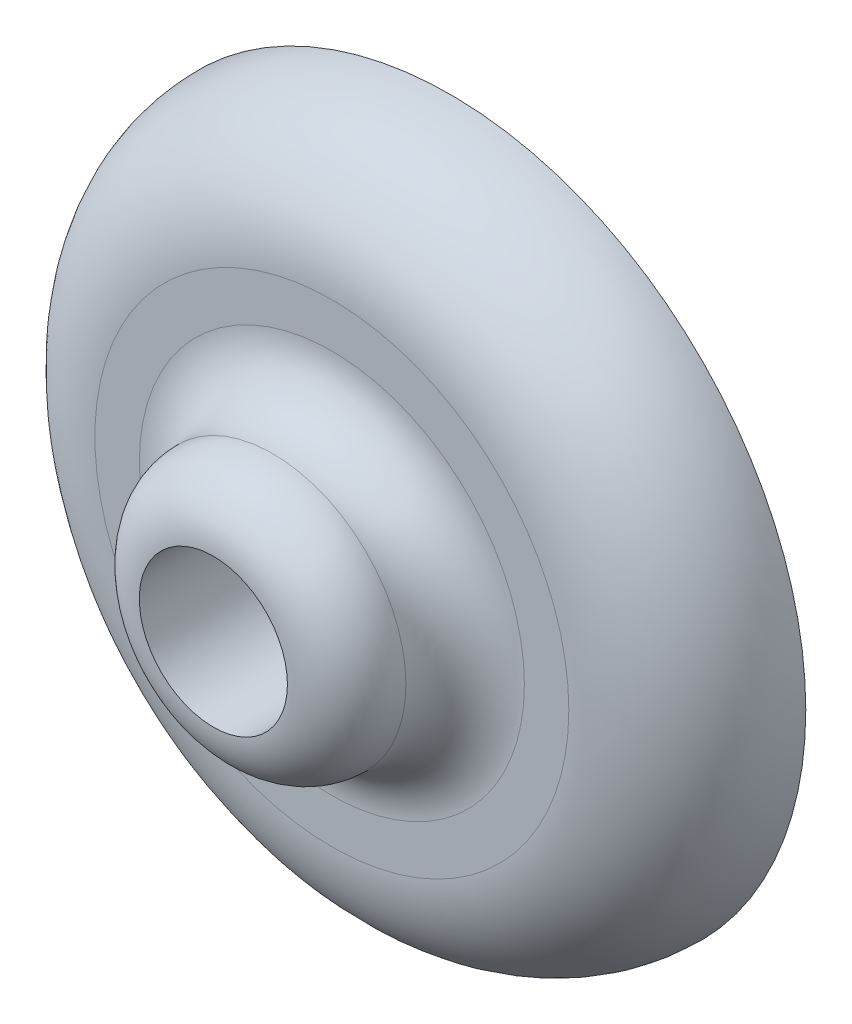
SolidWorks part; units mm, degrees
ref_plane "Front Plane" through (0, 0, 0) normal (0, 0, 1) x (1, 0, 0)
ref_plane "Top Plane" through (0, 0, 0) normal (0, 1, 0) x (1, 0, 0)
ref_plane "Right Plane" through (0, 0, 0) normal (1, 0, 0) x (0, 0, -1)
sketch "Sketch1" plane through (0, 0, 0) normal (0, 0, 1) x (1, 0, 0)
  circle A0 centre (0, 0) radius 1.25 construction
  circle A1 centre (0, 0) radius 6 construction
  circle A2 centre (0, 0) radius 1.25
  circle A3 centre (0, 0) radius 6
extrude "Boss-Extrude1" add sketch "Sketch1" along normal blind 2
sketch "Sketch2" plane through (0, 0, 2) normal (0, 0, 1) x (1, 0, 0)
  circle A0 centre (0, 0) radius 1.25 construction
  circle A1 centre (0, 0) radius 1.25
  circle A2 centre (0, 0) radius 2.25
  dimension "D1" = 4.5
extrude "Boss-Extrude2" add sketch "Sketch2" along normal blind 2
fillet "Fillet1" radius 1 2 edges at (2.25, 0, 2) (2.25, 0, 4)
fillet "Fillet2" radius 2 1 edges at (6, 0, 2)
